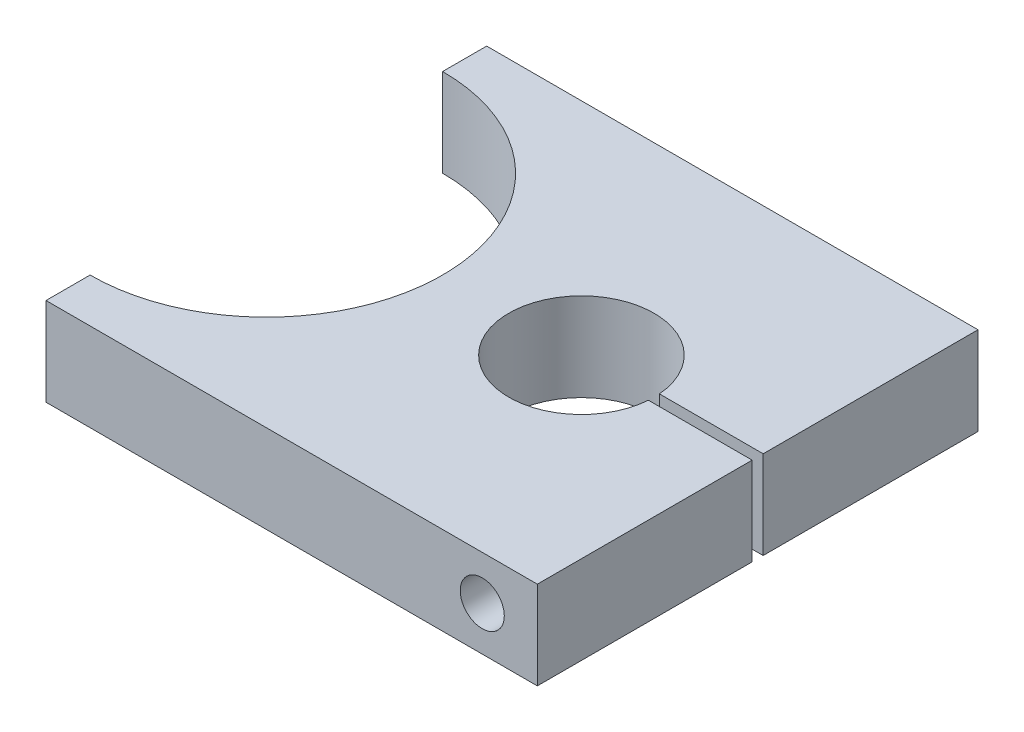
SolidWorks part; units mm, degrees
ref_plane "Front Plane" through (0, 0, 0) normal (0, 0, 1) x (1, 0, 0)
ref_plane "Top Plane" through (0, 0, 0) normal (0, 1, 0) x (1, 0, 0)
ref_plane "Right Plane" through (0, 0, 0) normal (1, 0, 0) x (0, 0, -1)
sketch "Sketch1" plane through (0, 0, 0) normal (0, 1, 0) x (1, 0, 0)
  line L0 (50.8, 127) -> (50.8, 0) construction
  line L1 (0, 0) -> (141.605, 0)
  line L2 (0, 0) -> (0, 12.7)
  line L3 (0, 127) -> (141.605, 127)
  line L5 (0, 114.3) -> (0, 127)
  line L6 (141.605, 0) -> (141.605, 127)
  line L7 (69.85, 63.5) -> (69.85, 0) construction
  arc A0 (0, 114.3) -> (0, 12.7) centre (0, 63.5) cw
  circle A1 centre (90.805, 63.5) radius 20.955
  point P7 (0, 114.3)
  point P8 (0, 12.7)
  dimension "D1" = 127
  dimension "D2" = 19.05
  dimension "D3" = 50.8
  dimension "D4" = 12.7
  dimension "D5" = 12.7
  dimension "D7" = 50.8
extrude "Boss-Extrude1" add sketch "Sketch1" along normal blind 25.4
sketch "Sketch2" plane through (0, 0, 0) normal (0, 0, 1) x (1, 0, 0)
  line L0 (141.605, 25.4) -> (141.605, 0) construction
  line L1 (0, 25.4) -> (141.605, 25.4) construction
  circle A0 centre (125.73, 12.7) radius 6.35
  dimension "D1" = 15.875
  dimension "D2" = 12.7
extrude "Cut-Extrude1" cut sketch "Sketch2" against normal through all
sketch "Sketch3" plane through (0, 25.4, 0) normal (0, 1, 0) x (1, 0, 0)
  line L0 (141.605, 0) -> (141.605, 127) construction
  line L1 (141.605, 65.0875) -> (111.125, 65.0875)
  line L2 (141.605, 65.0875) -> (141.605, 61.9125)
  line L3 (141.605, 61.9125) -> (111.125, 61.9125)
  line L4 (111.125, 65.0875) -> (111.125, 61.9125)
  line L5 (0, 0) -> (141.605, 0) construction
  dimension "D1" = 3.175
  dimension "D2" = 61.9125
  dimension "D3" = 30.48
extrude "Cut-Extrude2" cut sketch "Sketch3" against normal through all
